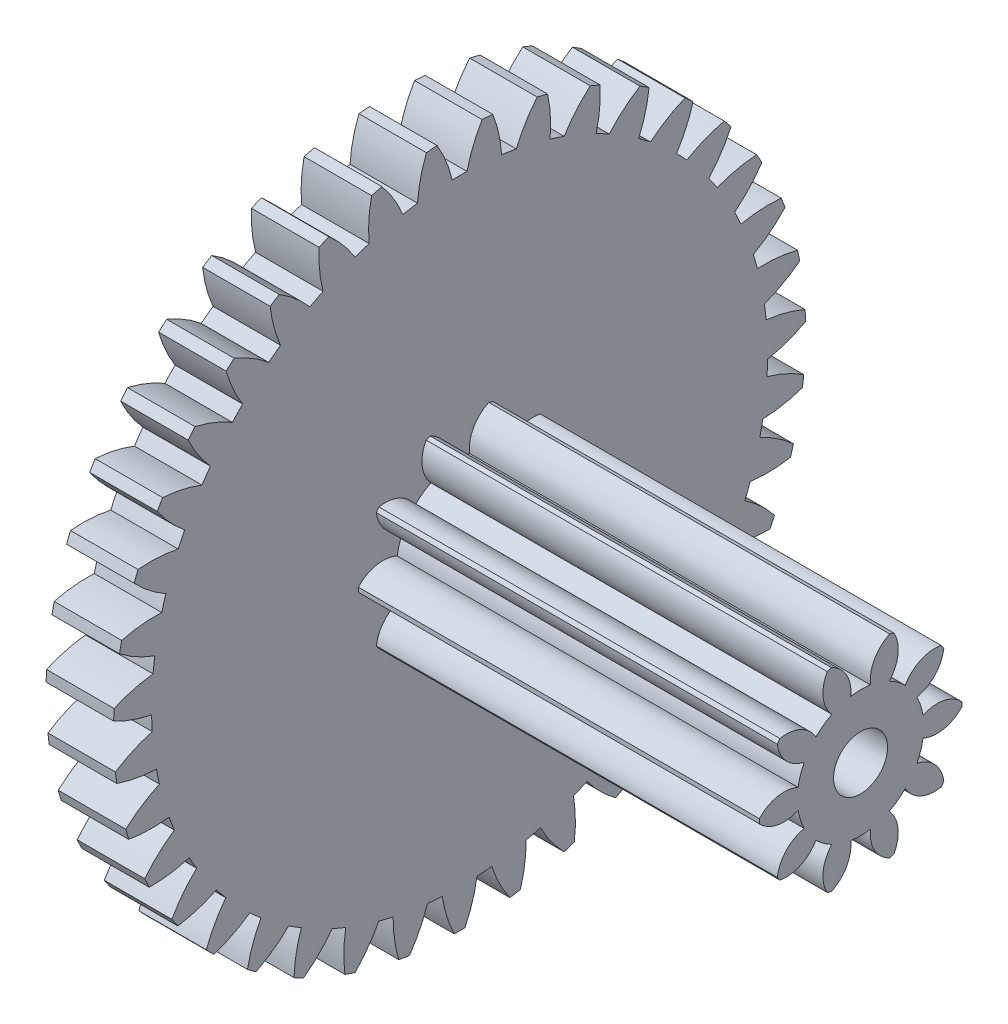
SolidWorks part; units mm, degrees
ref_plane "Plan de face" through (0, 0, 0) normal (0, 0, 1) x (1, 0, 0)
ref_plane "Plan de dessus" through (0, 0, 0) normal (0, 1, 0) x (1, 0, 0)
ref_plane "Plan de droite" through (0, 0, 0) normal (1, 0, 0) x (0, 0, -1)
ref_plane "Plan1" through (0, 0, 0) normal (0, 0, -1) x (-1, 0, 0)
sketch "Esquisse1" plane through (0, 0, 0) normal (0, 0, -1) x (-1, 0, 0)
  line L0 (-1, 5.125) -> (-1, 0)
  line L1 (-1, 0) -> (0, 0)
  line L2 (0, 0) -> (0, 5.125)
  line L3 (0, 5.125) -> (-1, 5.125)
  line L4 (-1, 0) -> (0, 0) construction
revolve "Révolution1" add sketch "Esquisse1" angle 360 about L4 reverse direction yes
sketch "Esquisse2" plane through (0, 0, 0) normal (-1, 0, 0) x (0, 0, 1)
  arc A0 (-0.4916, 5.1014) -> (-1.1491, 4.9945) centre (0, 0) ccw
  arc A1 (-1.1491, 4.9945) -> (-0.84, 4.4835) centre (-2.6433, 3.7415) cw
  arc A2 (-0.84, 4.4835) -> (-0.623, 4.5187) centre (0, 0) cw
  arc A3 (-0.623, 4.5187) -> (-0.4916, 5.1014) centre (1.3224, 4.386) cw
extrude "Enlèv. mat.-Extru.1" cut sketch "Esquisse2" against normal through all
sketch "Esquisse3" plane through (0, 0, 0) normal (-1, 0, 0) x (0, 0, 1)
  arc A0 (0.3331, 5.1142) -> (-0.3331, 5.1142) centre (0, 0) ccw
  arc A1 (-0.3331, 5.1142) -> (-0.1099, 4.5602) centre (-2.0089, 4.117) cw
  arc A2 (-0.1099, 4.5602) -> (0.1099, 4.5602) centre (0, 0) cw
  arc A3 (0.1099, 4.5602) -> (0.3331, 5.1142) centre (2.0089, 4.117) cw
extrude "Enlèv. mat.-Extru.2" cut sketch "Esquisse3" against normal through all
sketch "Esquisse4" plane through (0, 0, 0) normal (-1, 0, 0) x (0, 0, 1)
  arc A0 (1.1491, 4.9945) -> (0.4916, 5.1014) centre (0, 0) ccw
  arc A1 (0.4916, 5.1014) -> (0.623, 4.5187) centre (-1.3224, 4.386) cw
  arc A2 (0.623, 4.5187) -> (0.84, 4.4835) centre (0, 0) cw
  arc A3 (0.84, 4.4835) -> (1.1491, 4.9945) centre (2.6433, 3.7415) cw
extrude "Enlèv. mat.-Extru.3" cut sketch "Esquisse4" against normal through all
sketch "Esquisse5" plane through (0, 0, 0) normal (-1, 0, 0) x (0, 0, 1)
  arc A0 (1.9354, 4.7455) -> (1.3036, 4.9564) centre (0, 0) ccw
  arc A1 (1.3036, 4.9564) -> (1.3398, 4.3603) centre (-0.6017, 4.5413) cw
  arc A2 (1.3398, 4.3603) -> (1.5483, 4.2907) centre (0, 0) cw
  arc A3 (1.5483, 4.2907) -> (1.9354, 4.7455) centre (3.2092, 3.269) cw
extrude "Enlèv. mat.-Extru.4" cut sketch "Esquisse5" against normal through all
sketch "Esquisse6" plane through (0, 0, 0) normal (-1, 0, 0) x (0, 0, 1)
  arc A0 (2.6716, 4.3736) -> (2.0817, 4.6832) centre (0, 0) ccw
  arc A1 (2.0817, 4.6832) -> (2.0219, 4.0889) centre (0.1345, 4.579) cw
  arc A2 (2.0219, 4.0889) -> (2.2165, 3.9868) centre (0, 0) cw
  arc A3 (2.2165, 3.9868) -> (2.6716, 4.3736) centre (3.692, 2.7119) cw
extrude "Enlèv. mat.-Extru.5" cut sketch "Esquisse6" against normal through all
sketch "Esquisse7" plane through (0, 0, 0) normal (-1, 0, 0) x (0, 0, 1)
  arc A0 (3.3386, 3.8884) -> (2.806, 4.2886) centre (0, 0) ccw
  arc A1 (2.806, 4.2886) -> (2.6516, 3.7116) centre (0.8673, 4.4981) cw
  arc A2 (2.6516, 3.7116) -> (2.8273, 3.5796) centre (0, 0) cw
  arc A3 (2.8273, 3.5796) -> (3.3386, 3.8884) centre (4.0793, 2.0845) cw
extrude "Enlèv. mat.-Extru.6" cut sketch "Esquisse7" against normal through all
sketch "Esquisse8" plane through (0, 0, 0) normal (-1, 0, 0) x (0, 0, 1)
  arc A0 (3.9191, 3.3025) -> (3.4576, 3.7829) centre (0, 0) ccw
  arc A1 (3.4576, 3.7829) -> (3.2127, 3.2382) centre (1.5776, 4.3008) cw
  arc A2 (3.2127, 3.2382) -> (3.3649, 3.0797) centre (0, 0) cw
  arc A3 (3.3649, 3.0797) -> (3.9191, 3.3025) centre (4.3608, 1.4032) cw
extrude "Enlèv. mat.-Extru.7" cut sketch "Esquisse8" against normal through all
sketch "Esquisse9" plane through (0, 0, 0) normal (-1, 0, 0) x (0, 0, 1)
  arc A0 (4.3981, 2.6311) -> (4.0197, 3.1793) centre (0, 0) ccw
  arc A1 (4.0197, 3.1793) -> (3.6905, 2.6809) centre (2.2471, 3.992) cw
  arc A2 (3.6905, 2.6809) -> (3.8154, 2.5) centre (0, 0) cw
  arc A3 (3.8154, 2.5) -> (4.3981, 2.6311) centre (4.5294, 0.6855) cw
extrude "Enlèv. mat.-Extru.8" cut sketch "Esquisse9" against normal through all
sketch "Esquisse10" plane through (0, 0, 0) normal (-1, 0, 0) x (0, 0, 1)
  arc A0 (4.7632, 1.8915) -> (4.4776, 2.4933) centre (0, 0) ccw
  arc A1 (4.4776, 2.4933) -> (4.0728, 2.0542) centre (2.8584, 3.5799) cw
  arc A2 (4.0728, 2.0542) -> (4.167, 1.8556) centre (0, 0) cw
  arc A3 (4.167, 1.8556) -> (4.7632, 1.8915) centre (4.5807, -0.05) cw
extrude "Enlèv. mat.-Extru.9" cut sketch "Esquisse10" against normal through all
sketch "Esquisse11" plane through (0, 0, 0) normal (-1, 0, 0) x (0, 0, 1)
  arc A0 (5.0049, 1.1029) -> (4.8196, 1.7428) centre (0, 0) ccw
  arc A1 (4.8196, 1.7428) -> (4.3496, 1.3743) centre (3.3956, 3.075) cw
  arc A2 (4.3496, 1.3743) -> (4.4107, 1.1632) centre (0, 0) cw
  arc A3 (4.4107, 1.1632) -> (5.0049, 1.1029) centre (4.5134, -0.7841) cw
extrude "Enlèv. mat.-Extru.10" cut sketch "Esquisse11" against normal through all
sketch "Esquisse12" plane through (0, 0, 0) normal (-1, 0, 0) x (0, 0, 1)
  arc A0 (5.117, 0.2858) -> (5.0367, 0.9471) centre (0, 0) ccw
  arc A1 (5.0367, 0.9471) -> (4.5137, 0.6588) centre (3.8449, 2.4905) cw
  arc A2 (4.5137, 0.6588) -> (4.5402, 0.4406) centre (0, 0) cw
  arc A3 (4.5402, 0.4406) -> (5.117, 0.2858) centre (4.3292, -1.498) cw
extrude "Enlèv. mat.-Extru.11" cut sketch "Esquisse12" against normal through all
sketch "Esquisse13" plane through (0, 0, 0) normal (-1, 0, 0) x (0, 0, 1)
  arc A0 (5.0966, -0.5387) -> (5.1234, 0.1269) centre (0, 0) ccw
  arc A1 (5.1234, 0.1269) -> (4.5609, -0.0738) centre (4.1946, 1.8415) cw
  arc A2 (4.5609, -0.0738) -> (4.5521, -0.2934) centre (0, 0) cw
  arc A3 (4.5521, -0.2934) -> (5.0966, -0.5387) centre (4.0328, -2.173) cw
extrude "Enlèv. mat.-Extru.12" cut sketch "Esquisse13" against normal through all
sketch "Esquisse14" plane through (0, 0, 0) normal (-1, 0, 0) x (0, 0, 1)
  arc A0 (4.9442, -1.3493) -> (5.0774, -0.6966) centre (0, 0) ccw
  arc A1 (5.0774, -0.6966) -> (4.49, -0.8045) centre (4.4357, 1.1448) cw
  arc A2 (4.49, -0.8045) -> (4.446, -1.0198) centre (0, 0) cw
  arc A3 (4.446, -1.0198) -> (4.9442, -1.3493) centre (3.632, -2.7918) cw
extrude "Enlèv. mat.-Extru.13" cut sketch "Esquisse14" against normal through all
sketch "Esquisse15" plane through (0, 0, 0) normal (-1, 0, 0) x (0, 0, 1)
  arc A0 (4.6637, -2.1249) -> (4.8999, -1.5021) centre (0, 0) ccw
  arc A1 (4.8999, -1.5021) -> (4.3028, -1.5143) centre (4.5619, 0.4184) cw
  arc A2 (4.3028, -1.5143) -> (4.2249, -1.7198) centre (0, 0) cw
  arc A3 (4.2249, -1.7198) -> (4.6637, -2.1249) centre (3.1371, -3.3382) cw
extrude "Enlèv. mat.-Extru.14" cut sketch "Esquisse15" against normal through all
sketch "Esquisse16" plane through (0, 0, 0) normal (-1, 0, 0) x (0, 0, 1)
  arc A0 (4.2625, -2.8455) -> (4.5955, -2.2686) centre (0, 0) ccw
  arc A1 (4.5955, -2.2686) -> (4.0042, -2.1849) centre (4.5699, -0.3188) cw
  arc A2 (4.0042, -2.1849) -> (3.8943, -2.3753) centre (0, 0) cw
  arc A3 (3.8943, -2.3753) -> (4.2625, -2.8455) centre (2.561, -3.7982) cw
extrude "Enlèv. mat.-Extru.15" cut sketch "Esquisse16" against normal through all
sketch "Esquisse17" plane through (0, 0, 0) normal (-1, 0, 0) x (0, 0, 1)
  arc A0 (3.7508, -3.4924) -> (4.1721, -2.9764) centre (0, 0) ccw
  arc A1 (4.1721, -2.9764) -> (3.6018, -2.7989) centre (4.4596, -1.0477) cw
  arc A2 (3.6018, -2.7989) -> (3.4628, -2.9692) centre (0, 0) cw
  arc A3 (3.4628, -2.9692) -> (3.7508, -3.4924) centre (1.9186, -4.1599) cw
extrude "Enlèv. mat.-Extru.16" cut sketch "Esquisse17" against normal through all
sketch "Esquisse18" plane through (0, 0, 0) normal (-1, 0, 0) x (0, 0, 1)
  arc A0 (3.142, -4.0489) -> (3.6406, -3.6071) centre (0, 0) ccw
  arc A1 (3.6406, -3.6071) -> (3.1062, -3.3405) centre (4.2338, -1.7495) cw
  arc A2 (3.1062, -3.3405) -> (2.9417, -3.4862) centre (0, 0) cw
  arc A3 (2.9417, -3.4862) -> (3.142, -4.0489) centre (1.2264, -4.4138) cw
extrude "Enlèv. mat.-Extru.17" cut sketch "Esquisse18" against normal through all
sketch "Esquisse19" plane through (0, 0, 0) normal (-1, 0, 0) x (0, 0, 1)
  arc A0 (2.4518, -4.5005) -> (3.0149, -4.1444) centre (0, 0) ccw
  arc A1 (3.0149, -4.1444) -> (2.5301, -3.7955) centre (3.8983, -2.406) cw
  arc A2 (2.5301, -3.7955) -> (2.3444, -3.9129) centre (0, 0) cw
  arc A3 (2.3444, -3.9129) -> (2.4518, -4.5005) centre (0.5025, -4.5534) cw
extrude "Enlèv. mat.-Extru.18" cut sketch "Esquisse19" against normal through all
sketch "Esquisse20" plane through (0, 0, 0) normal (-1, 0, 0) x (0, 0, 1)
  arc A0 (1.6982, -4.8355) -> (2.311, -4.5744) centre (0, 0) ccw
  arc A1 (2.311, -4.5744) -> (1.8885, -4.1522) centre (3.4619, -3.0002) cw
  arc A2 (1.8885, -4.1522) -> (1.6863, -4.2383) centre (0, 0) cw
  arc A3 (1.6863, -4.2383) -> (1.6982, -4.8355) centre (-0.2344, -4.575) cw
extrude "Enlèv. mat.-Extru.19" cut sketch "Esquisse20" against normal through all
sketch "Esquisse21" plane through (0, 0, 0) normal (-1, 0, 0) x (0, 0, 1)
  arc A0 (0.9005, -5.0453) -> (1.5473, -4.8858) centre (0, 0) ccw
  arc A1 (1.5473, -4.8858) -> (1.198, -4.4014) centre (2.9358, -3.5167) cw
  arc A2 (1.198, -4.4014) -> (0.9846, -4.454) centre (0, 0) cw
  arc A3 (0.9846, -4.454) -> (0.9005, -5.0453) centre (-0.9652, -4.4782) cw
extrude "Enlèv. mat.-Extru.20" cut sketch "Esquisse21" against normal through all
sketch "Esquisse22" plane through (0, 0, 0) normal (-1, 0, 0) x (0, 0, 1)
  arc A0 (0.0795, -5.1244) -> (0.7435, -5.0708) centre (0, 0) ccw
  arc A1 (0.7435, -5.0708) -> (0.4765, -4.5365) centre (2.3336, -3.942) cw
  arc A2 (0.4765, -4.5365) -> (0.2574, -4.5542) centre (0, 0) cw
  arc A3 (0.2574, -4.5542) -> (0.0795, -5.1244) centre (-1.6711, -4.2653) cw
extrude "Enlèv. mat.-Extru.21" cut sketch "Esquisse22" against normal through all
sketch "Esquisse23" plane through (0, 0, 0) normal (-1, 0, 0) x (0, 0, 1)
  arc A0 (-0.7435, -5.0708) -> (-0.0795, -5.1244) centre (0, 0) ccw
  arc A1 (-0.0795, -5.1244) -> (-0.2574, -4.5542) centre (1.6711, -4.2653) cw
  arc A2 (-0.2574, -4.5542) -> (-0.4765, -4.5365) centre (0, 0) cw
  arc A3 (-0.4765, -4.5365) -> (-0.7435, -5.0708) centre (-2.3336, -3.942) cw
extrude "Enlèv. mat.-Extru.22" cut sketch "Esquisse23" against normal through all
sketch "Esquisse24" plane through (0, 0, 0) normal (-1, 0, 0) x (0, 0, 1)
  arc A0 (-1.5473, -4.8858) -> (-0.9005, -5.0453) centre (0, 0) ccw
  arc A1 (-0.9005, -5.0453) -> (-0.9846, -4.454) centre (0.9652, -4.4782) cw
  arc A2 (-0.9846, -4.454) -> (-1.198, -4.4014) centre (0, 0) cw
  arc A3 (-1.198, -4.4014) -> (-1.5473, -4.8858) centre (-2.9358, -3.5167) cw
extrude "Enlèv. mat.-Extru.23" cut sketch "Esquisse24" against normal through all
sketch "Esquisse25" plane through (0, 0, 0) normal (-1, 0, 0) x (0, 0, 1)
  arc A0 (-2.311, -4.5744) -> (-1.6982, -4.8355) centre (0, 0) ccw
  arc A1 (-1.6982, -4.8355) -> (-1.6863, -4.2383) centre (0.2344, -4.575) cw
  arc A2 (-1.6863, -4.2383) -> (-1.8885, -4.1522) centre (0, 0) cw
  arc A3 (-1.8885, -4.1522) -> (-2.311, -4.5744) centre (-3.4619, -3.0002) cw
extrude "Enlèv. mat.-Extru.24" cut sketch "Esquisse25" against normal through all
sketch "Esquisse26" plane through (0, 0, 0) normal (-1, 0, 0) x (0, 0, 1)
  arc A0 (-3.0149, -4.1444) -> (-2.4518, -4.5005) centre (0, 0) ccw
  arc A1 (-2.4518, -4.5005) -> (-2.3444, -3.9129) centre (-0.5025, -4.5534) cw
  arc A2 (-2.3444, -3.9129) -> (-2.5301, -3.7955) centre (0, 0) cw
  arc A3 (-2.5301, -3.7955) -> (-3.0149, -4.1444) centre (-3.8983, -2.406) cw
extrude "Enlèv. mat.-Extru.25" cut sketch "Esquisse26" against normal through all
sketch "Esquisse27" plane through (0, 0, 0) normal (-1, 0, 0) x (0, 0, 1)
  arc A0 (-3.6406, -3.6071) -> (-3.142, -4.0489) centre (0, 0) ccw
  arc A1 (-3.142, -4.0489) -> (-2.9417, -3.4862) centre (-1.2264, -4.4138) cw
  arc A2 (-2.9417, -3.4862) -> (-3.1062, -3.3405) centre (0, 0) cw
  arc A3 (-3.1062, -3.3405) -> (-3.6406, -3.6071) centre (-4.2338, -1.7495) cw
extrude "Enlèv. mat.-Extru.26" cut sketch "Esquisse27" against normal through all
sketch "Esquisse28" plane through (0, 0, 0) normal (-1, 0, 0) x (0, 0, 1)
  arc A0 (-4.1721, -2.9764) -> (-3.7508, -3.4924) centre (0, 0) ccw
  arc A1 (-3.7508, -3.4924) -> (-3.4628, -2.9692) centre (-1.9186, -4.1599) cw
  arc A2 (-3.4628, -2.9692) -> (-3.6018, -2.7989) centre (0, 0) cw
  arc A3 (-3.6018, -2.7989) -> (-4.1721, -2.9764) centre (-4.4596, -1.0477) cw
extrude "Enlèv. mat.-Extru.27" cut sketch "Esquisse28" against normal through all
sketch "Esquisse29" plane through (0, 0, 0) normal (-1, 0, 0) x (0, 0, 1)
  arc A0 (-4.5955, -2.2686) -> (-4.2625, -2.8455) centre (0, 0) ccw
  arc A1 (-4.2625, -2.8455) -> (-3.8943, -2.3753) centre (-2.561, -3.7982) cw
  arc A2 (-3.8943, -2.3753) -> (-4.0042, -2.1849) centre (0, 0) cw
  arc A3 (-4.0042, -2.1849) -> (-4.5955, -2.2686) centre (-4.5699, -0.3188) cw
extrude "Enlèv. mat.-Extru.28" cut sketch "Esquisse29" against normal through all
sketch "Esquisse30" plane through (0, 0, 0) normal (-1, 0, 0) x (0, 0, 1)
  arc A0 (-4.8999, -1.5021) -> (-4.6637, -2.1249) centre (0, 0) ccw
  arc A1 (-4.6637, -2.1249) -> (-4.2249, -1.7198) centre (-3.1371, -3.3382) cw
  arc A2 (-4.2249, -1.7198) -> (-4.3028, -1.5143) centre (0, 0) cw
  arc A3 (-4.3028, -1.5143) -> (-4.8999, -1.5021) centre (-4.5619, 0.4184) cw
extrude "Enlèv. mat.-Extru.29" cut sketch "Esquisse30" against normal through all
sketch "Esquisse31" plane through (0, 0, 0) normal (-1, 0, 0) x (0, 0, 1)
  arc A0 (-5.0774, -0.6966) -> (-4.9442, -1.3493) centre (0, 0) ccw
  arc A1 (-4.9442, -1.3493) -> (-4.446, -1.0198) centre (-3.632, -2.7918) cw
  arc A2 (-4.446, -1.0198) -> (-4.49, -0.8045) centre (0, 0) cw
  arc A3 (-4.49, -0.8045) -> (-5.0774, -0.6966) centre (-4.4357, 1.1448) cw
extrude "Enlèv. mat.-Extru.30" cut sketch "Esquisse31" against normal through all
sketch "Esquisse32" plane through (0, 0, 0) normal (-1, 0, 0) x (0, 0, 1)
  arc A0 (-5.1234, 0.1269) -> (-5.0966, -0.5387) centre (0, 0) ccw
  arc A1 (-5.0966, -0.5387) -> (-4.5521, -0.2934) centre (-4.0328, -2.173) cw
  arc A2 (-4.5521, -0.2934) -> (-4.5609, -0.0738) centre (0, 0) cw
  arc A3 (-4.5609, -0.0738) -> (-5.1234, 0.1269) centre (-4.1946, 1.8415) cw
extrude "Enlèv. mat.-Extru.31" cut sketch "Esquisse32" against normal through all
sketch "Esquisse33" plane through (0, 0, 0) normal (-1, 0, 0) x (0, 0, 1)
  arc A0 (-5.0367, 0.9471) -> (-5.117, 0.2858) centre (0, 0) ccw
  arc A1 (-5.117, 0.2858) -> (-4.5402, 0.4406) centre (-4.3292, -1.498) cw
  arc A2 (-4.5402, 0.4406) -> (-4.5137, 0.6588) centre (0, 0) cw
  arc A3 (-4.5137, 0.6588) -> (-5.0367, 0.9471) centre (-3.8449, 2.4905) cw
extrude "Enlèv. mat.-Extru.32" cut sketch "Esquisse33" against normal through all
sketch "Esquisse34" plane through (0, 0, 0) normal (-1, 0, 0) x (0, 0, 1)
  arc A0 (-4.8196, 1.7428) -> (-5.0049, 1.1029) centre (0, 0) ccw
  arc A1 (-5.0049, 1.1029) -> (-4.4107, 1.1632) centre (-4.5134, -0.7841) cw
  arc A2 (-4.4107, 1.1632) -> (-4.3496, 1.3743) centre (0, 0) cw
  arc A3 (-4.3496, 1.3743) -> (-4.8196, 1.7428) centre (-3.3956, 3.075) cw
extrude "Enlèv. mat.-Extru.33" cut sketch "Esquisse34" against normal through all
sketch "Esquisse35" plane through (0, 0, 0) normal (-1, 0, 0) x (0, 0, 1)
  arc A0 (-4.4776, 2.4933) -> (-4.7632, 1.8915) centre (0, 0) ccw
  arc A1 (-4.7632, 1.8915) -> (-4.167, 1.8556) centre (-4.5807, -0.05) cw
  arc A2 (-4.167, 1.8556) -> (-4.0728, 2.0542) centre (0, 0) cw
  arc A3 (-4.0728, 2.0542) -> (-4.4776, 2.4933) centre (-2.8584, 3.5799) cw
extrude "Enlèv. mat.-Extru.34" cut sketch "Esquisse35" against normal through all
sketch "Esquisse36" plane through (0, 0, 0) normal (-1, 0, 0) x (0, 0, 1)
  arc A0 (-4.0197, 3.1793) -> (-4.3981, 2.6311) centre (0, 0) ccw
  arc A1 (-4.3981, 2.6311) -> (-3.8154, 2.5) centre (-4.5294, 0.6855) cw
  arc A2 (-3.8154, 2.5) -> (-3.6905, 2.6809) centre (0, 0) cw
  arc A3 (-3.6905, 2.6809) -> (-4.0197, 3.1793) centre (-2.2471, 3.992) cw
extrude "Enlèv. mat.-Extru.35" cut sketch "Esquisse36" against normal through all
sketch "Esquisse37" plane through (0, 0, 0) normal (-1, 0, 0) x (0, 0, 1)
  arc A0 (-3.4576, 3.7829) -> (-3.9191, 3.3025) centre (0, 0) ccw
  arc A1 (-3.9191, 3.3025) -> (-3.3649, 3.0797) centre (-4.3608, 1.4032) cw
  arc A2 (-3.3649, 3.0797) -> (-3.2127, 3.2382) centre (0, 0) cw
  arc A3 (-3.2127, 3.2382) -> (-3.4576, 3.7829) centre (-1.5776, 4.3008) cw
extrude "Enlèv. mat.-Extru.36" cut sketch "Esquisse37" against normal through all
sketch "Esquisse38" plane through (0, 0, 0) normal (-1, 0, 0) x (0, 0, 1)
  arc A0 (-2.806, 4.2886) -> (-3.3386, 3.8884) centre (0, 0) ccw
  arc A1 (-3.3386, 3.8884) -> (-2.8273, 3.5796) centre (-4.0793, 2.0845) cw
  arc A2 (-2.8273, 3.5796) -> (-2.6516, 3.7116) centre (0, 0) cw
  arc A3 (-2.6516, 3.7116) -> (-2.806, 4.2886) centre (-0.8673, 4.4981) cw
extrude "Enlèv. mat.-Extru.37" cut sketch "Esquisse38" against normal through all
sketch "Esquisse39" plane through (0, 0, 0) normal (-1, 0, 0) x (0, 0, 1)
  arc A0 (-2.0817, 4.6832) -> (-2.6716, 4.3736) centre (0, 0) ccw
  arc A1 (-2.6716, 4.3736) -> (-2.2165, 3.9868) centre (-3.692, 2.7119) cw
  arc A2 (-2.2165, 3.9868) -> (-2.0219, 4.0889) centre (0, 0) cw
  arc A3 (-2.0219, 4.0889) -> (-2.0817, 4.6832) centre (-0.1345, 4.579) cw
extrude "Enlèv. mat.-Extru.38" cut sketch "Esquisse39" against normal through all
sketch "Esquisse40" plane through (0, 0, 0) normal (-1, 0, 0) x (0, 0, 1)
  arc A0 (-1.3036, 4.9564) -> (-1.9354, 4.7455) centre (0, 0) ccw
  arc A1 (-1.9354, 4.7455) -> (-1.5483, 4.2907) centre (-3.2092, 3.269) cw
  arc A2 (-1.5483, 4.2907) -> (-1.3398, 4.3603) centre (0, 0) cw
  arc A3 (-1.3398, 4.3603) -> (-1.3036, 4.9564) centre (0.6017, 4.5413) cw
extrude "Enlèv. mat.-Extru.39" cut sketch "Esquisse40" against normal through all
sketch "Esquisse41" plane through (1, 0, 0) normal (1, 0, 0) x (0, 0, -1)
  arc A0 (0.6621, 0.6623) -> (1.1939, 0.9081) centre (1.098, 0.4174) cw
  arc A1 (1.1939, 0.9081) -> (1.2326, 0.8548) centre (0, 0) cw
  arc A2 (1.2326, 0.8548) -> (0.8345, 0.425) centre (0.7362, 0.9152) cw
  arc A3 (0.8345, 0.425) -> (0.9249, 0.1467) centre (0, 0) cw
  arc A4 (0.9249, 0.1467) -> (1.4996, 0.0329) centre (1.1336, -0.3077) cw
  arc A5 (1.4996, 0.0329) -> (1.4996, -0.0329) centre (0, 0) cw
  arc A6 (1.4996, -0.0329) -> (0.9249, -0.1467) centre (1.1336, 0.3077) cw
  arc A7 (0.9249, -0.1467) -> (0.8345, -0.425) centre (0, 0) cw
  arc A8 (0.8345, -0.425) -> (1.2326, -0.8548) centre (0.7362, -0.9152) cw
  arc A9 (1.2326, -0.8548) -> (1.1939, -0.9081) centre (0, 0) cw
  arc A10 (1.1939, -0.9081) -> (0.6621, -0.6623) centre (1.098, -0.4174) cw
  arc A11 (0.6621, -0.6623) -> (0.4253, -0.8343) centre (0, 0) cw
  arc A12 (0.4253, -0.8343) -> (0.4947, -1.4161) centre (0.0577, -1.1732) cw
  arc A13 (0.4947, -1.4161) -> (0.4321, -1.4364) centre (0, 0) cw
  arc A14 (0.4321, -1.4364) -> (0.1463, -0.925) centre (0.6429, -0.983) cw
  arc A15 (0.1463, -0.925) -> (-0.1463, -0.925) centre (0, 0) cw
  arc A16 (-0.1463, -0.925) -> (-0.4321, -1.4364) centre (-0.6429, -0.983) cw
  arc A17 (-0.4321, -1.4364) -> (-0.4947, -1.4161) centre (0, 0) cw
  arc A18 (-0.4947, -1.4161) -> (-0.4253, -0.8343) centre (-0.0577, -1.1732) cw
  arc A19 (-0.4253, -0.8343) -> (-0.6621, -0.6623) centre (0, 0) cw
  arc A20 (-0.6621, -0.6623) -> (-1.1939, -0.9081) centre (-1.098, -0.4174) cw
  arc A21 (-1.1939, -0.9081) -> (-1.2326, -0.8548) centre (0, 0) cw
  arc A22 (-1.2326, -0.8548) -> (-0.8345, -0.425) centre (-0.7362, -0.9152) cw
  arc A23 (-0.8345, -0.425) -> (-0.9249, -0.1467) centre (0, 0) cw
  arc A24 (-0.9249, -0.1467) -> (-1.4996, -0.0329) centre (-1.1336, 0.3077) cw
  arc A25 (-1.4996, -0.0329) -> (-1.4996, 0.0329) centre (0, 0) cw
  arc A26 (-1.4996, 0.0329) -> (-0.9249, 0.1467) centre (-1.1336, -0.3077) cw
  arc A27 (-0.9249, 0.1467) -> (-0.8345, 0.425) centre (0, 0) cw
  arc A28 (-0.8345, 0.425) -> (-1.2326, 0.8548) centre (-0.7362, 0.9152) cw
  arc A29 (-1.2326, 0.8548) -> (-1.1939, 0.9081) centre (0, 0) cw
  arc A30 (-1.1939, 0.9081) -> (-0.6621, 0.6623) centre (-1.098, 0.4174) cw
  arc A31 (-0.6621, 0.6623) -> (-0.4253, 0.8343) centre (0, 0) cw
  arc A32 (-0.4253, 0.8343) -> (-0.4947, 1.4161) centre (-0.0577, 1.1732) cw
  arc A33 (-0.4947, 1.4161) -> (-0.4321, 1.4364) centre (0, 0) cw
  arc A34 (-0.4321, 1.4364) -> (-0.1463, 0.925) centre (-0.6429, 0.983) cw
  arc A35 (-0.1463, 0.925) -> (0.1463, 0.925) centre (0, 0) cw
  arc A36 (0.1463, 0.925) -> (0.4321, 1.4364) centre (0.6429, 0.983) cw
  arc A37 (0.4321, 1.4364) -> (0.4947, 1.4161) centre (0, 0) cw
  arc A38 (0.4947, 1.4161) -> (0.4253, 0.8343) centre (0.0577, 1.1732) cw
  arc A39 (0.4253, 0.8343) -> (0.6621, 0.6623) centre (0, 0) cw
extrude "Boss.-Extru.1" add sketch "Esquisse41" along normal blind 5.9385
hole_wizard "Diamètre du perçage Ø0.8 (0.8)1" positions "Esquisse43" profile "Esquisse42" hole size "Ø0.8" standard "Ansi Metric"
sketch "Esquisse43" plane through (0, 0, 0) normal (-1, 0, 0) x (0, 0, 1)
  point P0 (0, 0)
sketch "Esquisse42" plane through (0, 0, 0) normal (0, 1, 0) x (0, 0, 1)
  line L0 (0, 0) -> (0, 6.9385)
  line L1 (0, 6.9385) -> (0.4, 6.9385)
  line L2 (0.4, 6.9385) -> (0.4, 0)
  line L5 (0.4, 0) -> (0, 0)
  line L11 (0, -6.35) -> (0, 107.95) construction
  dimension "Diamètre du perçage jusqu'au prochain" = 0.8
  dimension "Profondeur du perçage jusqu'au prochain" = 6.9385
